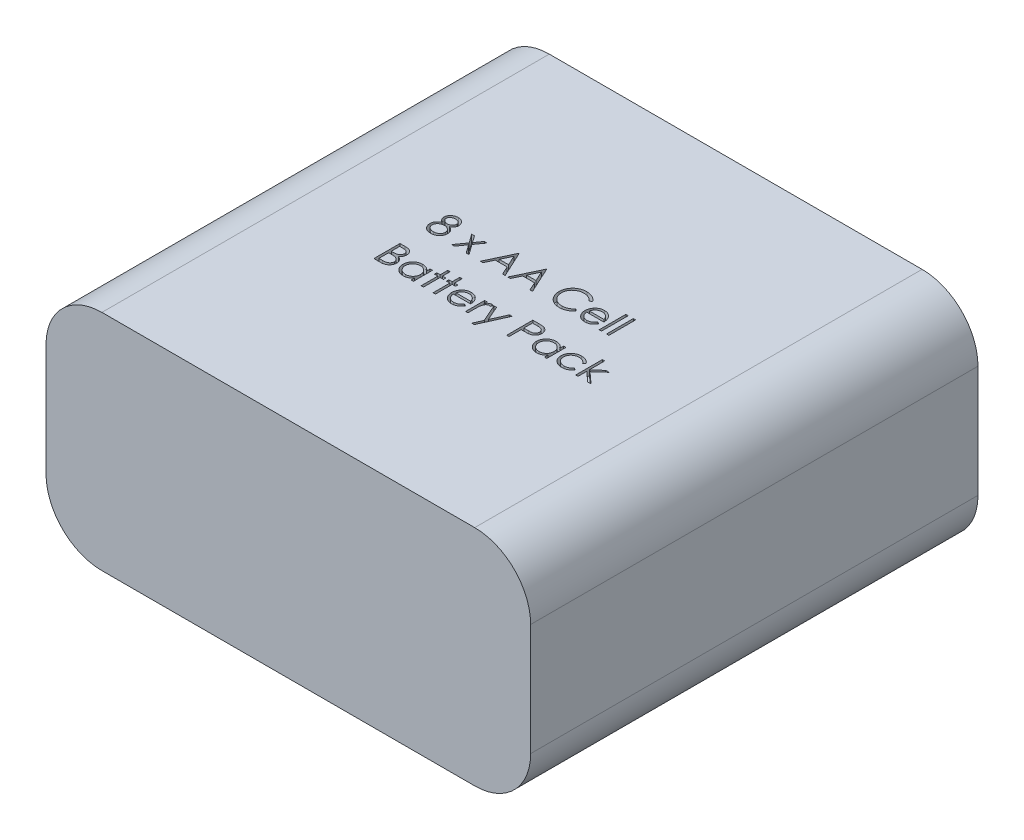
SolidWorks part; units mm, degrees
ref_plane "Front Plane" through (0, 0, 0) normal (0, 0, 1) x (1, 0, 0)
ref_plane "Top Plane" through (0, 0, 0) normal (0, 1, 0) x (1, 0, 0)
ref_plane "Right Plane" through (0, 0, 0) normal (1, 0, 0) x (0, 0, -1)
sketch "Sketch1" plane through (0, 0, 0) normal (0, 0, 1) x (1, 0, 0)
  line L1 (0, 0) -> (65, 0)
  line L2 (0, 0) -> (0, 30)
  line L3 (0, 30) -> (65, 30)
  line L4 (65, 0) -> (65, 30)
  dimension "D1" = 65
  dimension "D2" = 30
extrude "Boss-Extrude1" add sketch "Sketch1" against normal blind 60
fillet "Fillet1" radius 7.5 4 edges at (0, 0, -30) (0, 30, -30) (65, 0, -30) (65, 30, -30)
sketch "Sketch2" plane through (0, 30, 0) normal (0, 1, 0) x (1, 0, 0)
  text T0 "8 x AA Cell \r\nBattery Pack"
  point P1 (16.345, 33.057)
  point P2 (21.5377, 31.23)
  point P3 (19.0375, 31.3261)
extrude "Cut-Extrude1" cut sketch "Sketch2" against normal blind 1
